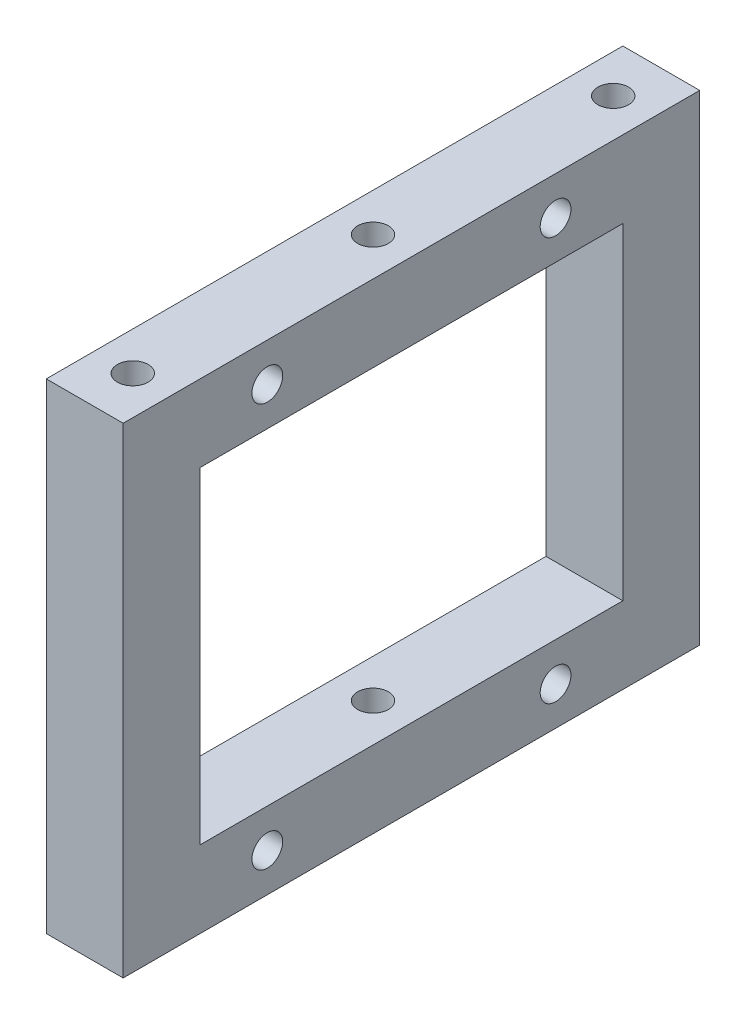
SolidWorks part; units mm, degrees
material "6061 合金"
ref_plane "前视基准面" through (0, 0, 0) normal (0, 0, 1) x (1, 0, 0)
ref_plane "上视基准面" through (0, 0, 0) normal (0, 1, 0) x (1, 0, 0)
ref_plane "右视基准面" through (0, 0, 0) normal (1, 0, 0) x (0, 0, -1)
sketch "草图1" plane through (0, 0, 0) normal (1, 0, 0) x (0, 0, -1)
  line L0 (30, 50) -> (30, 0) construction
  line L1 (0, 0) -> (60, 0)
  line L2 (0, 0) -> (0, 50)
  line L3 (0, 50) -> (60, 50)
  line L4 (60, 0) -> (60, 50)
  line L5 (15, 46) -> (45, 46) construction
  line L6 (15, 46) -> (15, 4) construction
  line L7 (15, 4) -> (45, 4) construction
  line L8 (45, 46) -> (45, 4) construction
  line L9 (0, 25) -> (60, 25) construction
  line L11 (8, 42) -> (52, 42)
  line L12 (8, 42) -> (8, 8)
  line L13 (8, 8) -> (52, 8)
  line L14 (52, 42) -> (52, 8)
  circle A0 centre (15, 46) radius 1.6
  circle A1 centre (45, 46) radius 1.6
  circle A2 centre (15, 4) radius 1.6
  circle A3 centre (45, 4) radius 1.6
  point P13 (30, 46)
  point P14 (15, 25)
  point P23 (30, 42)
  point P24 (8, 25)
  dimension "D3" = 3.2
  dimension "D1" = 50
  dimension "D2" = 60
  dimension "D4" = 4
  dimension "D5" = 30
  dimension "D6" = 4
  dimension "D7" = 8
extrude "凸台-拉伸1" add sketch "草图1" along normal blind 8
cosmetic thread "装饰螺纹线14"
cosmetic thread "装饰螺纹线15"
cosmetic thread "装饰螺纹线16"
cosmetic thread "装饰螺纹线17"
sketch "草图2" plane through (0, 0, 0) normal (0, -1, 0) x (1, 0, 0)
  line L0 (4, -5) -> (4, -55) construction
  line L1 (8, 0) -> (0, 0) construction
  line L2 (8, -60) -> (0, -60) construction
  line L3 (0, 0) -> (0, -60) construction
  circle A0 centre (4, -5) radius 1.6
  circle A1 centre (4, -30) radius 1.6
  circle A2 centre (4, -55) radius 1.6
  point P6 (4, -30)
  dimension "D1" = 3.2
  dimension "D2" = 5
  dimension "D3" = 5
  dimension "D4" = 4
extrude "切除-拉伸1" cut sketch "草图2" against normal blind 10
cosmetic thread "装饰螺纹线18" parameters "D2"=4
cosmetic thread "装饰螺纹线19" parameters "D2"=4
cosmetic thread "装饰螺纹线20" parameters "D2"=4
extrude "切除-拉伸2" cut sketch "草图2<2>" along normal blind 10 from surface starting at face at (4, 50, -30)
sketch "草图2<2>" plane through (0, 0, 0) normal (0, -1, 0) x (1, 0, 0) same geometry as "草图2"
cosmetic thread "装饰螺纹线11" parameters "D2"=4
cosmetic thread "装饰螺纹线12" parameters "D2"=4
cosmetic thread "装饰螺纹线13" parameters "D2"=4
